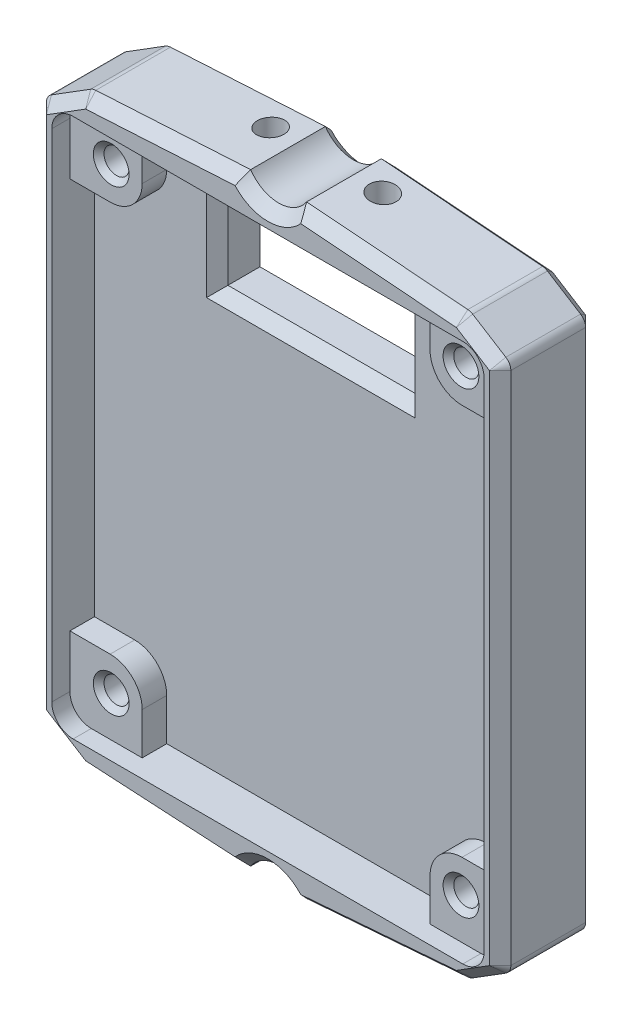
SolidWorks part; units mm, degrees
ref_plane "Front Plane" through (0, 0, 0) normal (0, 0, 1) x (1, 0, 0)
ref_plane "Top Plane" through (0, 0, 0) normal (0, 1, 0) x (1, 0, 0)
ref_plane "Right Plane" through (0, 0, 0) normal (1, 0, 0) x (0, 0, -1)
sketch "Sketch1" plane through (0, 0, 0) normal (0, 0, 1) x (1, 0, 0)
  line L0 (-23.25, 28.25) -> (-23.25, -28.25)
  line L1 (-20.25, 25.25) -> (20.25, 25.25)
  line L2 (-20.25, 25.25) -> (-20.25, -25.25)
  line L3 (-20.25, -25.25) -> (20.25, -25.25)
  line L4 (20.25, 25.25) -> (20.25, -25.25)
  line L5 (-20.25, 25.25) -> (20.25, -25.25) construction
  line L6 (-20.25, -25.25) -> (20.25, 25.25) construction
  line L7 (-23.25, -28.25) -> (23.25, -28.25)
  line L8 (23.25, 28.25) -> (23.25, -28.25)
  line L9 (-23.25, 28.25) -> (23.25, 28.25)
  point P0 (0, 0)
  dimension "D1" = 50.5
  dimension "D2" = 40.5
  dimension "D3" = 3
extrude "Boss-Extrude1" add sketch "Sketch1" along normal blind 4
sketch "Sketch2" plane through (0, 0, 0) normal (0, 0, -1) x (-1, 0, 0)
  line L1 (-23.25, 28.25) -> (23.25, 28.25)
  line L2 (-23.25, 28.25) -> (-23.25, -28.25)
  line L3 (-23.25, -28.25) -> (23.25, -28.25)
  line L4 (23.25, 28.25) -> (23.25, -28.25)
extrude "Boss-Extrude2" add sketch "Sketch2" along normal blind 5
sketch "Sketch3" plane through (0, 0, 0) normal (0, 0, 1) x (1, 0, 0)
  line L0 (0, 0) -> (0, 30.8352) construction
  line L1 (0, 0) -> (-31.9704, 0) construction
  line L2 (-20.25, 25.25) -> (-20.25, 18.3322)
  line L3 (-20.25, 25.25) -> (-20.25, -25.25) construction
  line L4 (-20.25, 18.3322) -> (-13.4806, 18.3322)
  line L5 (-13.4806, 18.3322) -> (-13.4806, 25.25)
  line L6 (20.25, 25.25) -> (-20.25, 25.25) construction
  line L7 (-13.4806, 25.25) -> (-20.25, 25.25)
  line L8 (13.4806, 25.25) -> (20.25, 25.25)
  line L9 (13.4806, 18.3322) -> (13.4806, 25.25)
  line L10 (20.25, 18.3322) -> (13.4806, 18.3322)
  line L11 (20.25, 25.25) -> (20.25, 18.3322)
  line L12 (20.25, -25.25) -> (20.25, -18.3322)
  line L13 (20.25, -18.3322) -> (13.4806, -18.3322)
  line L14 (13.4806, -18.3322) -> (13.4806, -25.25)
  line L15 (13.4806, -25.25) -> (20.25, -25.25)
  line L16 (-13.4806, -25.25) -> (-20.25, -25.25)
  line L17 (-13.4806, -18.3322) -> (-13.4806, -25.25)
  line L18 (-20.25, -18.3322) -> (-13.4806, -18.3322)
  line L19 (-20.25, -25.25) -> (-20.25, -18.3322)
  circle A0 centre (-16.38, 21.46) radius 1.175
  circle A1 centre (16.38, 21.46) radius 1.175
  circle A2 centre (16.38, -21.46) radius 1.175
  circle A3 centre (-16.38, -21.46) radius 1.175
  dimension "D3" = 2.35
  dimension "D1" = 21.46
  dimension "D2" = 16.38
extrude "Boss-Extrude3" add sketch "Sketch3" along normal blind 2.3
chamfer "Chamfer3" distance 4.5 angle 58 4 edges at (-23.25, -28.25, -0.5) (23.25, -28.25, -0.5) (-23.25, 28.25, -0.5) (23.25, 28.25, -0.5) first distance on face at (-23.25, 0, -0.5) first distance on face at (23.25, 0, -0.5)
fillet "Fillet1" radius 3 4 edges at (13.4806, -18.3322, 1.15) (-13.4806, -18.3322, 1.15) (13.4806, 18.3322, 1.15) (-13.4806, 18.3322, 1.15)
sketch "Sketch4" plane through (0, 0, 0) normal (0, 0, 1) x (1, 0, 0)
  line L0 (20.25, 25.25) -> (-20.25, 25.25) construction
  line L1 (-8.75, 23.8) -> (8.75, 23.8)
  line L2 (-8.75, 23.8) -> (-8.75, 13.8)
  line L3 (-8.75, 13.8) -> (8.75, 13.8)
  line L4 (8.75, 23.8) -> (8.75, 13.8)
  point P4 (0, 13.8)
  dimension "D1" = 10
  dimension "D2" = 1.45
  dimension "D3" = 17.5
extrude "Cut-Extrude1" cut sketch "Sketch4" against normal through all
sketch "Sketch5" plane through (0, 0, -5) normal (0, 0, -1) x (-1, 0, 0)
  line L0 (-29.5901, 0) -> (35.962, 0) construction
  line L4 (0, 42.4173) -> (0, 14.6256) construction
  line L8 (-23.25, -28.25) -> (23.25, -28.25)
  line L9 (23.25, -28.25) -> (23.25, -27.0847)
  line L10 (23.25, -27.0847) -> (2.6192, -28.25)
  line L11 (-23.25, -26.638) -> (-2.6192, -28.25)
  line L12 (-23.25, -28.25) -> (-23.25, -26.638)
  line L14 (16.0485, 28.25) -> (-16.0485, 28.25) construction
  line L15 (-2.6192, 28.25) -> (2.6192, 28.25)
  line L16 (-23.25, 28.25) -> (-23.25, 26.638)
  line L17 (-23.25, 26.638) -> (-2.6192, 28.25)
  line L18 (23.25, 27.0847) -> (2.6192, 28.25)
  line L19 (23.25, 28.25) -> (23.25, 27.0847)
  line L20 (-23.25, 28.25) -> (23.25, 28.25)
  arc A0 (-2.6192, 28.25) -> (2.6192, 28.25) centre (0, 30) ccw
  arc A1 (-2.6192, -28.25) -> (2.6192, -28.25) centre (0, -30) cw
  line M10 (-16.0485, -28.25) -> (16.0485, -28.25)
  line M12 (16.0485, 28.25) -> (-16.0485, 28.25)
  line M22 (16.0485, -28.25) -> (23.25, -23.75)
  line M23 (23.25, 23.75) -> (16.0485, 28.25)
  line M24 (-16.0485, 28.25) -> (-23.25, 23.75)
  line M25 (-23.25, -23.75) -> (-16.0485, -28.25)
  dimension "D1" = 6.3
  dimension "D3" = 60
extrude "Cut-Extrude2" cut sketch "Sketch5" against normal through all contours L12 L8 L11 M25 | A1 L8 | L9 L10 L8 M22 | L11 M25 M10 | L10 L8 M22 | L17 M24 M12 | L18 M23 M12 | L20 L18 L19 M23 | L20 L16 L17 M24 | A0 M12 | L11 A1 L10 L9 L8 L12 region at (20.2805, -27.5835, -5) region at (-12.0169, -27.972, -5) region at (0, -27.6777, -5) region at (12.2118, -27.8502, -5) region at (-20.1718, -27.7652, -5) region at (-12.0169, 27.972, -5) region at (12.2118, 27.8502, -5) region at (0, 27.6777, -5) region at (20.2805, 27.5835, -5) region at (-20.1718, 27.7652, -5)
sketch "Sketch6" plane through (0, 0, 4) normal (0, 0, 1) x (1, 0, 0)
  line L0 (-17.3831, -27.4161) -> (-2.6192, -28.25) construction
  line L1 (-23.2503, 33.2078) -> (-21.7503, 33.2078)
  line L2 (-23.2503, 33.2078) -> (-23.2503, -27.1694)
  line L3 (-23.2503, -27.1694) -> (-21.7503, -27.1694)
  line L4 (-21.7503, 33.2078) -> (-21.7503, -27.1694)
  line L5 (0, 0) -> (0, 31.5361) construction
  line L6 (21.7503, 33.2078) -> (21.7503, -27.1694)
  line L7 (23.2503, -27.1694) -> (21.7503, -27.1694)
  line L8 (23.2503, 33.2078) -> (23.2503, -27.1694)
  line L9 (23.2503, 33.2078) -> (21.7503, 33.2078)
  dimension "D1" = 1.5
extrude "Cut-Extrude3" cut sketch "Sketch6" against normal through all
sketch "Sketch7" plane through (0, 0, 0) normal (0, 1, 0) x (1, 0, 0)
  line L0 (-5.25, 1.5) -> (5.25, 1.5) construction
  line L1 (2.6192, 5) -> (-2.6192, 5) construction
  circle A0 centre (-5.25, 1.5) radius 1.25
  circle A1 centre (5.25, 1.5) radius 1.25
  point P4 (0, 1.5)
  dimension "D1" = 2.5
  dimension "D2" = 10.5
  dimension "D3" = 3.5
extrude "Cut-Extrude4" cut sketch "Sketch7" against normal blind 10 from offset 30
mirror "Mirror1" about plane through (0, 0, 0) normal (0, 1, 0) of "Cut-Extrude4"
fillet "Fillet2" radius 1 8 edges at (21.7503, -24.6871, -0.5) (17.9677, -27.0507, -0.5) (-17.3831, -27.4161, -0.5) (-21.7503, -24.6871, -0.5) (-21.7503, 24.6871, -0.5) (21.7503, 24.6871, -0.5) (-17.3831, 27.4161, -0.5) (17.9677, 27.0507, -0.5)
chamfer "Chamfer1" distance 1 angle 45 48 edges at (0, -26.85, 4) (0, 26.85, 4) (-9.8731, -27.8403, 4) (-21.7503, 0, 4) (10.1713, -27.6599, 4) (21.7503, 0, 4) (0, 23.8, 0) (-8.75, 18.8, 0) (8.75, 18.8, 0) (0, 13.8, 0) (0, 26.85, -5) (8.75, 18.8, -5) (0, 13.8, -5) (-8.75, 18.8, -5) (0, 23.8, -5) (-21.7503, 0, -5) (21.7503, 0, -5) (-9.8731, -27.8403, -5) (0, -26.85, -5) (10.1713, -27.6599, -5) (-17.3733, -27.3852, 4) (-19.4404, -26.1305, 4) (-19.4404, 26.1305, 4) (-21.6249, -24.6176, 4) (-21.6249, 24.6176, 4) (17.9585, -27.0226, 4) (19.7279, 25.9509, 4) (19.7279, -25.9509, 4) (21.6249, 24.6176, 4) (21.6249, -24.6176, 4) (-19.4404, 26.1305, -5) (19.7279, 25.9509, -5) (-21.6249, 24.6176, -5) (21.6249, 24.6176, -5) (-21.6249, -24.6176, -5) (21.6249, -24.6176, -5) (-19.4404, -26.1305, -5) (19.7279, -25.9509, -5) (-17.3733, -27.3852, -5) (17.9585, -27.0226, -5) (-9.8731, 27.8403, 4) (-17.3733, 27.3852, 4) (10.1713, 27.6599, 4) (17.9585, 27.0226, 4) (-9.8731, 27.8403, -5) (10.1713, 27.6599, -5) (-17.3733, 27.3852, -5) (17.9585, 27.0226, -5)
fillet "Fillet3" radius 2 4 edges at (-20.25, -25.25, 2.8088) (20.25, -25.25, 2.8088) (20.25, 25.25, 2.8088) (-20.25, 25.25, 2.8088)
sketch "Sketch8" plane through (0, 0, 2.3) normal (0, 0, 1) x (1, 0, 0)
  circle A0 centre (-16.38, 21.46) radius 1.175
  circle A1 centre (16.38, 21.46) radius 1.175
  circle A2 centre (16.38, -21.46) radius 1.175
  circle A3 centre (-16.38, -21.46) radius 1.175
  circle A4 centre (-16.38, 21.46) radius 1.175 construction
extrude "Cut-Extrude5" cut sketch "Sketch8" against normal through all
sketch "Sketch9" plane through (0, 0, -5) normal (0, 0, -1) x (-1, 0, 0)
  line L0 (0, 9.9819) -> (0, -23.9909) construction
  line L1 (-16.3742, -2.0365) -> (-6.3848, -2.0365)
  line L2 (-12.6187, -3.5365) -> (-6.3848, -3.5365)
  line L3 (-16.3742, -2.0365) -> (0, -17.5995)
  line L4 (-12.6187, -3.5365) -> (0, -15.5301)
  line L5 (-4, -2.7865) -> (-12.6323, -2.7865) construction
  line L6 (12.6187, -3.5365) -> (0, -15.5301)
  line L7 (16.3742, -2.0365) -> (0, -17.5995)
  line L8 (12.6187, -3.5365) -> (6.3848, -3.5365)
  line L9 (16.3742, -2.0365) -> (6.3848, -2.0365)
  arc A0 (-6.3848, -3.5365) -> (-6.3848, -2.0365) centre (-4, -2.7865) ccw
  arc A1 (6.3848, -3.5365) -> (6.3848, -2.0365) centre (4, -2.7865) cw
  dimension "D1" = 5
  dimension "D2" = 1.5
  dimension "D3" = 1.5
  dimension "D4" = 8
extrude "Cut-Extrude6" cut sketch "Sketch9" against normal blind 1
chamfer "Chamfer2" distance 0.5 angle 45 4 edges at (-17.555, -21.46, 2.3) (17.555, -21.46, 2.3) (15.205, 21.46, 2.3) (-15.205, 21.46, 2.3)
